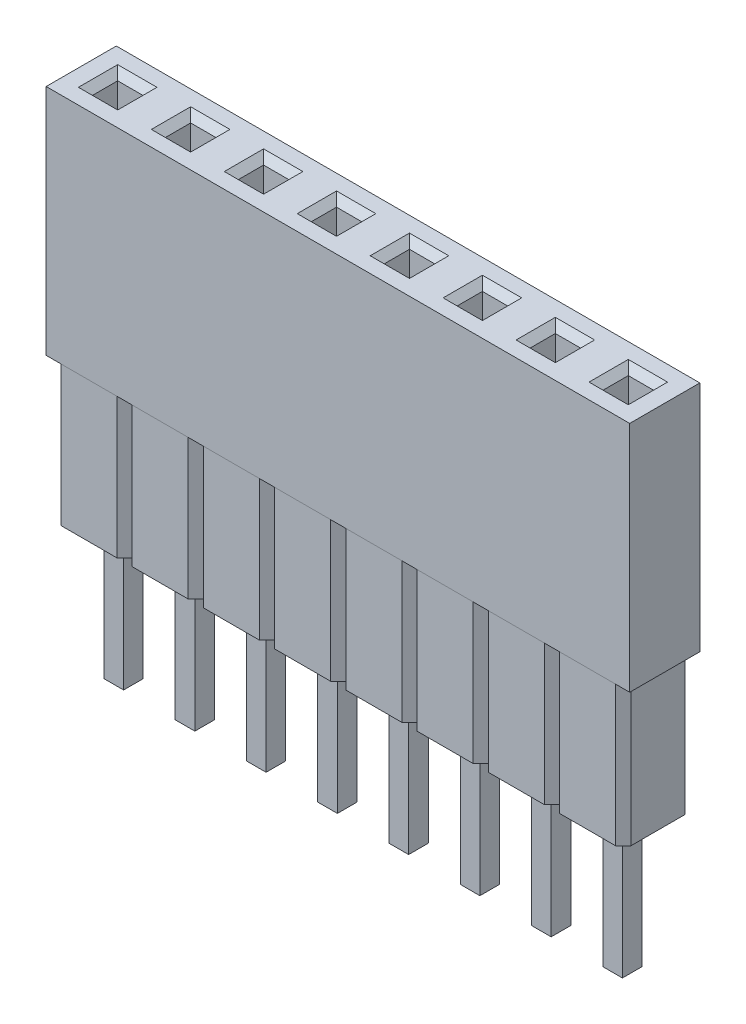
SolidWorks part; units mm, degrees
ref_plane "Alzado" through (0, 0, 0) normal (0, 0, 1) x (1, 0, 0)
ref_plane "Planta" through (0, 0, 0) normal (0, 1, 0) x (1, 0, 0)
ref_plane "Vista lateral" through (0, 0, 0) normal (1, 0, 0) x (0, 0, -1)
sketch "Croquis1" plane through (0, 0, 0) normal (0, 1, 0) x (1, 0, 0)
  line L1 (-10.4, 1.25) -> (10.4, 1.25)
  line L2 (-10.4, 1.25) -> (-10.4, -1.25)
  line L3 (-10.4, -1.25) -> (10.4, -1.25)
  line L4 (10.4, 1.25) -> (10.4, -1.25)
  line L5 (-10.4, 1.25) -> (10.4, -1.25) construction
  line L6 (-10.4, -1.25) -> (10.4, 1.25) construction
  point P0 (0, 0)
  dimension "D1" = 20.8
  dimension "D2" = 2.5
extrude "Saliente-Extruir1" add sketch "Croquis1" along normal blind 8.3
sketch "Croquis3" plane through (0, 8.3, 0) normal (0, 1, 0) x (1, 0, 0)
  line L0 (-10.4, 0) -> (-7.8, 0) construction
  line L1 (-10.4, 1.25) -> (-10.4, -1.25) construction
  line L2 (-7.8, 0) -> (-5.2, 0) construction
  line L3 (-5.2, 0) -> (-2.6, 0) construction
  line L4 (-2.6, 0) -> (0, 0) construction
  line L5 (0, 0) -> (2.6, 0) construction
  line L6 (2.6, 0) -> (5.2, 0) construction
  line L7 (5.2, 0) -> (7.8, 0) construction
  line L8 (7.8, 0) -> (10.4, 0) construction
  line L9 (10.4, -1.25) -> (10.4, 1.25) construction
  line L10 (-9.1, 0) -> (-9.1, 1.25) construction
  line L11 (10.4, 1.25) -> (-10.4, 1.25) construction
  line L12 (-6.5, 0) -> (-6.5, 1.25) construction
  line L13 (-3.9, 0) -> (-3.9, 1.25) construction
  line L14 (-1.3, 0) -> (-1.3, 1.25) construction
  line L15 (1.3, 0) -> (1.3, 1.25) construction
  line L16 (3.9, 0) -> (3.9, 1.25) construction
  line L17 (6.5, 0) -> (6.5, 1.25) construction
  line L18 (9.1, 0) -> (9.1, 1.25) construction
  line L19 (9.1, 1.25) -> (9.0931, 1.2533) construction
  line L21 (-9.8, 0.7) -> (-8.4, 0.7)
  line L22 (-9.8, 0.7) -> (-9.8, -0.7)
  line L23 (-9.8, -0.7) -> (-8.4, -0.7)
  line L24 (-8.4, 0.7) -> (-8.4, -0.7)
  line L25 (-9.8, 0.7) -> (-8.4, -0.7) construction
  line L26 (-9.8, -0.7) -> (-8.4, 0.7) construction
  line L27 (-7.2, 0.7) -> (-5.8, 0.7)
  line L28 (-7.2, 0.7) -> (-7.2, -0.7)
  line L29 (-7.2, -0.7) -> (-5.8, -0.7)
  line L30 (-5.8, 0.7) -> (-5.8, -0.7)
  line L31 (-7.2, 0.7) -> (-5.8, -0.7) construction
  line L32 (-7.2, -0.7) -> (-5.8, 0.7) construction
  line L33 (-4.6, 0.7) -> (-3.2, 0.7)
  line L34 (-4.6, 0.7) -> (-4.6, -0.7)
  line L35 (-4.6, -0.7) -> (-3.2, -0.7)
  line L36 (-3.2, 0.7) -> (-3.2, -0.7)
  line L37 (-4.6, 0.7) -> (-3.2, -0.7) construction
  line L38 (-4.6, -0.7) -> (-3.2, 0.7) construction
  line L39 (-2, 0.7) -> (-0.6, 0.7)
  line L40 (-2, 0.7) -> (-2, -0.7)
  line L41 (-2, -0.7) -> (-0.6, -0.7)
  line L42 (-0.6, 0.7) -> (-0.6, -0.7)
  line L43 (-2, 0.7) -> (-0.6, -0.7) construction
  line L44 (-2, -0.7) -> (-0.6, 0.7) construction
  line L45 (0.6, 0.7) -> (2, 0.7)
  line L46 (0.6, 0.7) -> (0.6, -0.7)
  line L47 (0.6, -0.7) -> (2, -0.7)
  line L48 (2, 0.7) -> (2, -0.7)
  line L49 (0.6, 0.7) -> (2, -0.7) construction
  line L50 (0.6, -0.7) -> (2, 0.7) construction
  line L51 (3.2, 0.7) -> (4.6, 0.7)
  line L52 (3.2, 0.7) -> (3.2, -0.7)
  line L53 (3.2, -0.7) -> (4.6, -0.7)
  line L54 (4.6, 0.7) -> (4.6, -0.7)
  line L55 (3.2, 0.7) -> (4.6, -0.7) construction
  line L56 (3.2, -0.7) -> (4.6, 0.7) construction
  line L57 (5.8, 0.7) -> (7.2, 0.7)
  line L58 (5.8, 0.7) -> (5.8, -0.7)
  line L59 (5.8, -0.7) -> (7.2, -0.7)
  line L60 (7.2, 0.7) -> (7.2, -0.7)
  line L61 (5.8, 0.7) -> (7.2, -0.7) construction
  line L62 (5.8, -0.7) -> (7.2, 0.7) construction
  line L63 (8.4, 0.7) -> (9.8, 0.7)
  line L64 (8.4, 0.7) -> (8.4, -0.7)
  line L65 (8.4, -0.7) -> (9.8, -0.7)
  line L66 (9.8, 0.7) -> (9.8, -0.7)
  line L67 (8.4, 0.7) -> (9.8, -0.7) construction
  line L68 (8.4, -0.7) -> (9.8, 0.7) construction
  dimension "D1" = 2.6
  dimension "D2" = 2.6
  dimension "D3" = 2.6
  dimension "D4" = 2.6
  dimension "D5" = 2.6
  dimension "D6" = 2.6
  dimension "D7" = 2.6
  dimension "D8" = 2.6
  dimension "D9" = 1.4
  dimension "D10" = 1.4
  dimension "D11" = 1.4
  dimension "D12" = 1.4
  dimension "D13" = 1.4
  dimension "D14" = 1.4
  dimension "D15" = 1.4
  dimension "D16" = 1.4
  dimension "D17" = 1.4
  dimension "D18" = 1.4
  dimension "D19" = 1.4
  dimension "D20" = 1.4
  dimension "D21" = 1.4
  dimension "D22" = 1.4
  dimension "D23" = 1.4
  dimension "D24" = 1.4
extrude "Cortar-Extruir1" cut sketch "Croquis3" against normal blind 0.5
sketch "Croquis4" plane through (0, 7.8, 0) normal (0, 1, 0) x (1, 0, 0)
  line L0 (-9.8, 0) -> (9.8, 0) construction
  line L1 (-9.8, 0.7) -> (-9.8, -0.7) construction
  line L2 (9.8, -0.7) -> (9.8, 0.7) construction
  line L3 (9.1, 0.7) -> (9.1, -0.7) construction
  line L4 (9.8, 0.7) -> (8.4, 0.7) construction
  line L5 (8.4, -0.7) -> (9.8, -0.7) construction
  line L6 (6.5, 0.7) -> (6.5, -0.7) construction
  line L7 (7.2, 0.7) -> (5.8, 0.7) construction
  line L8 (5.8, -0.7) -> (7.2, -0.7) construction
  line L9 (3.9, 0.7) -> (3.9, -0.7) construction
  line L12 (1.3, 0.7) -> (1.3, -0.7) construction
  line L13 (2, 0.7) -> (0.6, 0.7) construction
  line L14 (0.6, -0.7) -> (2, -0.7) construction
  line L15 (4.6, 0.7) -> (3.2, 0.7) construction
  line L16 (3.2, -0.7) -> (4.6, -0.7) construction
  line L17 (-1.3, -0.7) -> (-1.3, 0.7) construction
  line L18 (-0.6, 0.7) -> (-2, 0.7) construction
  line L20 (-2, -0.7) -> (-0.6, -0.7) construction
  line L21 (-3.9, 0.7) -> (-3.9, -0.7) construction
  line L22 (-3.2, 0.7) -> (-4.6, 0.7) construction
  line L23 (-4.6, -0.7) -> (-3.2, -0.7) construction
  line L24 (-6.5, 0.7) -> (-6.5, -0.7) construction
  line L25 (-5.8, 0.7) -> (-7.2, 0.7) construction
  line L26 (-7.2, -0.7) -> (-5.8, -0.7) construction
  line L27 (-9.1, 0.7) -> (-9.1, -0.7) construction
  line L28 (-8.4, 0.7) -> (-9.8, 0.7) construction
  line L29 (-9.8, -0.7) -> (-8.4, -0.7) construction
  line L30 (-9.1, 0) -> (-6.5, 0) construction
  line L31 (-9.55, 0.45) -> (-8.65, 0.45)
  line L32 (-9.55, 0.45) -> (-9.55, -0.45)
  line L33 (-9.55, -0.45) -> (-8.65, -0.45)
  line L34 (-8.65, 0.45) -> (-8.65, -0.45)
  line L35 (-9.55, 0.45) -> (-8.65, -0.45) construction
  line L36 (-9.55, -0.45) -> (-8.65, 0.45) construction
  line L37 (-6.95, 0.45) -> (-6.05, 0.45)
  line L38 (-6.95, 0.45) -> (-6.95, -0.45)
  line L39 (-6.95, -0.45) -> (-6.05, -0.45)
  line L40 (-6.05, 0.45) -> (-6.05, -0.45)
  line L41 (-6.95, 0.45) -> (-6.05, -0.45) construction
  line L42 (-6.95, -0.45) -> (-6.05, 0.45) construction
  line L43 (-3.45, -0.45) -> (-4.35, -0.45)
  line L44 (-3.45, -0.45) -> (-3.45, 0.45)
  line L45 (-3.45, 0.45) -> (-4.35, 0.45)
  line L46 (-4.35, -0.45) -> (-4.35, 0.45)
  line L47 (-3.45, -0.45) -> (-4.35, 0.45) construction
  line L48 (-3.45, 0.45) -> (-4.35, -0.45) construction
  line L49 (-0.85, -0.45) -> (-1.75, -0.45)
  line L50 (-0.85, -0.45) -> (-0.85, 0.45)
  line L51 (-0.85, 0.45) -> (-1.75, 0.45)
  line L52 (-1.75, -0.45) -> (-1.75, 0.45)
  line L53 (-0.85, -0.45) -> (-1.75, 0.45) construction
  line L54 (-0.85, 0.45) -> (-1.75, -0.45) construction
  line L55 (1.75, -0.45) -> (0.85, -0.45)
  line L56 (1.75, -0.45) -> (1.75, 0.45)
  line L57 (1.75, 0.45) -> (0.85, 0.45)
  line L58 (0.85, -0.45) -> (0.85, 0.45)
  line L59 (1.75, -0.45) -> (0.85, 0.45) construction
  line L60 (1.75, 0.45) -> (0.85, -0.45) construction
  line L61 (4.35, -0.45) -> (3.45, -0.45)
  line L62 (4.35, -0.45) -> (4.35, 0.45)
  line L63 (4.35, 0.45) -> (3.45, 0.45)
  line L64 (3.45, -0.45) -> (3.45, 0.45)
  line L65 (4.35, -0.45) -> (3.45, 0.45) construction
  line L66 (4.35, 0.45) -> (3.45, -0.45) construction
  line L67 (6.05, 0.45) -> (6.95, 0.45)
  line L68 (6.05, 0.45) -> (6.05, -0.45)
  line L69 (6.05, -0.45) -> (6.95, -0.45)
  line L70 (6.95, 0.45) -> (6.95, -0.45)
  line L71 (6.05, 0.45) -> (6.95, -0.45) construction
  line L72 (6.05, -0.45) -> (6.95, 0.45) construction
  line L73 (8.65, 0.45) -> (9.55, 0.45)
  line L74 (8.65, 0.45) -> (8.65, -0.45)
  line L75 (8.65, -0.45) -> (9.55, -0.45)
  line L76 (9.55, 0.45) -> (9.55, -0.45)
  line L77 (8.65, 0.45) -> (9.55, -0.45) construction
  line L78 (8.65, -0.45) -> (9.55, 0.45) construction
  point P54 (-9.1, 0)
  point P59 (-6.5, 0)
  point P64 (-3.9, 0)
  point P69 (-1.3, 0)
  point P74 (1.3, 0)
  point P79 (3.9, 0)
  point P84 (6.5, 0)
  point P89 (9.1, 0)
  dimension "D1" = 0.9
  dimension "D2" = 0.9
  dimension "D3" = 0.9
  dimension "D4" = 0.9
  dimension "D5" = 0.9
  dimension "D6" = 0.9
  dimension "D7" = 0.9
  dimension "D8" = 0.9
  dimension "D9" = 0.9
  dimension "D10" = 0.9
  dimension "D11" = 0.9
  dimension "D12" = 0.9
  dimension "D13" = 0.9
  dimension "D14" = 0.9
  dimension "D15" = 0.9
  dimension "D16" = 0.9
extrude "Cortar-Extruir2" cut sketch "Croquis4" against normal blind 6.5
chamfer "Chaflán2" distance 0.5 angle 45 4 edges at (-9.1, 7.8, 0.7) (-8.4, 7.8, 0) (-9.8, 7.8, 0) (-9.1, 7.8, -0.7)
chamfer "Chaflán3" distance 0.5 angle 45 4 edges at (-6.5, 7.8, 0.7) (-7.2, 7.8, 0) (-5.8, 7.8, 0) (-6.5, 7.8, -0.7)
chamfer "Chaflán4" distance 0.5 angle 45 4 edges at (-3.9, 7.8, 0.7) (-3.2, 7.8, 0) (-3.9, 7.8, -0.7) (-4.6, 7.8, 0)
chamfer "Chaflán5" distance 0.5 angle 45 4 edges at (-0.6, 7.8, 0) (-1.3, 7.8, -0.7) (-2, 7.8, 0) (-1.3, 7.8, 0.7)
chamfer "Chaflán6" distance 0.5 angle 45 4 edges at (1.3, 7.8, 0.7) (0.6, 7.8, 0) (1.3, 7.8, -0.7) (2, 7.8, 0)
chamfer "Chaflán7" distance 0.5 angle 45 4 edges at (4.6, 7.8, 0) (3.9, 7.8, -0.7) (3.9, 7.8, 0.7) (3.2, 7.8, 0)
chamfer "Chaflán8" distance 0.5 angle 45 4 edges at (6.5, 7.8, 0.7) (7.2, 7.8, 0) (6.5, 7.8, -0.7) (5.8, 7.8, 0)
chamfer "Chaflán9" distance 0.5 angle 45 4 edges at (9.8, 7.8, 0) (9.1, 7.8, -0.7) (8.4, 7.8, 0) (9.1, 7.8, 0.7)
sketch "Croquis5" plane through (0, 0, 0) normal (0, -1, 0) x (1, 0, 0)
  line L0 (-10.4, 0) -> (0, 0) construction
  line L1 (-10.4, -1.25) -> (-10.4, 1.25) construction
  line L2 (0, 0) -> (0, 1.25) construction
  line L3 (-10.4, 1.25) -> (10.4, 1.25) construction
  line L5 (-10.16, 1.24) -> (10.16, 1.24)
  line L6 (-10.16, 1.24) -> (-10.16, -1.24)
  line L7 (-10.16, -1.24) -> (10.16, -1.24)
  line L8 (10.16, 1.24) -> (10.16, -1.24)
  line L9 (-10.16, 1.24) -> (10.16, -1.24) construction
  line L10 (-10.16, -1.24) -> (10.16, 1.24) construction
  dimension "D1" = 20.32
  dimension "D2" = 2.48
extrude "Saliente-Extruir2" add sketch "Croquis5" along normal blind 5
sketch "Croquis6" plane through (0, -5, 0) normal (0, -1, 0) x (1, 0, 0)
  line L0 (-10.16, 1.24) -> (-7.62, 1.24) construction
  line L1 (10.16, 1.24) -> (-10.16, 1.24) construction
  line L2 (-7.62, 1.24) -> (-5.08, 1.24) construction
  line L3 (10.16, 1.24) -> (-10.16, 1.24) construction
  line L4 (-5.08, 1.24) -> (-2.54, 1.24) construction
  line L5 (-2.54, 1.24) -> (0, 1.24) construction
  line L6 (0, 1.24) -> (2.54, 1.24) construction
  line L7 (2.54, 1.24) -> (5.08, 1.24) construction
  line L8 (5.08, 1.24) -> (7.62, 1.24) construction
  line L9 (-10.16, 0) -> (10.16, 0) construction
  line L10 (-10.16, 1.24) -> (-10.16, -1.24) construction
  line L11 (10.16, -1.24) -> (10.16, 1.24) construction
  line L12 (-10.16, 1.24) -> (-10.16, 0.97)
  line L13 (-10.16, 0.97) -> (-9.89, 1.24)
  line L14 (-9.89, 1.24) -> (-10.16, 1.24)
  line L15 (-10.16, -1.24) -> (-10.16, -0.97)
  line L16 (-10.16, -0.97) -> (-9.89, -1.24)
  line L17 (-10.16, -1.24) -> (10.16, -1.24) construction
  line L18 (-9.89, -1.24) -> (-10.16, -1.24)
  line L19 (-10.16, 0.97) -> (10.16, 0.97) construction
  line L20 (-10.16, -0.97) -> (10.16, -0.97) construction
  line L21 (-7.62, 1.24) -> (-7.89, 1.24)
  line L22 (-7.89, 1.24) -> (-7.62, 0.97)
  line L23 (-7.62, 0.97) -> (-7.35, 1.24)
  line L24 (-7.35, 1.24) -> (-7.62, 1.24)
  line L25 (-5.08, 1.24) -> (-5.35, 1.24)
  line L26 (-5.35, 1.24) -> (-5.08, 0.97)
  line L27 (-5.08, 0.97) -> (-4.81, 1.24)
  line L28 (-4.81, 1.24) -> (-5.08, 1.24)
  line L29 (-2.54, 1.24) -> (-2.81, 1.24)
  line L30 (-2.81, 1.24) -> (-2.54, 0.97)
  line L31 (-2.54, 0.97) -> (-2.27, 1.24)
  line L32 (-2.27, 1.24) -> (-2.54, 1.24)
  line L33 (0, 1.24) -> (-0.27, 1.24)
  line L34 (-0.27, 1.24) -> (0, 0.97)
  line L35 (0, 0.97) -> (0.27, 1.24)
  line L36 (0.27, 1.24) -> (0, 1.24)
  line L37 (2.54, 1.24) -> (2.27, 1.24)
  line L38 (2.27, 1.24) -> (2.54, 0.97)
  line L39 (2.54, 0.97) -> (2.81, 1.24)
  line L40 (2.81, 1.24) -> (2.54, 1.24)
  line L41 (5.08, 1.24) -> (4.81, 1.24)
  line L42 (4.81, 1.24) -> (5.08, 0.97)
  line L43 (5.08, 0.97) -> (5.35, 1.24)
  line L44 (5.35, 1.24) -> (5.08, 1.24)
  line L45 (7.62, 1.24) -> (7.35, 1.24)
  line L46 (7.35, 1.24) -> (7.62, 0.97)
  line L47 (7.62, 0.97) -> (7.89, 1.24)
  line L48 (7.89, 1.24) -> (7.62, 1.24)
  line L49 (10.16, 1.24) -> (9.89, 1.24)
  line L50 (9.89, 1.24) -> (10.16, 0.97)
  line L51 (10.16, 0.97) -> (10.16, 1.24)
  line L52 (10.16, -1.24) -> (9.89, -1.24)
  line L53 (9.89, -1.24) -> (10.16, -0.97)
  line L54 (10.16, -0.97) -> (10.16, -1.24)
  line L56 (7.62, -0.97) -> (7.35, -1.24)
  line L57 (7.35, -1.24) -> (7.62, -1.25)
  line L58 (10.4, -1.25) -> (-10.4, -1.25) construction
  line L59 (7.62, -1.25) -> (7.89, -1.24)
  line L60 (7.89, -1.24) -> (7.62, -0.97)
  line L61 (5.08, -0.97) -> (5.35, -1.24)
  line L62 (-10.16, -1.24) -> (10.16, -1.24) construction
  line L63 (5.35, -1.24) -> (4.81, -1.24)
  line L64 (4.81, -1.24) -> (5.08, -0.97)
  line L65 (2.54, -0.97) -> (2.27, -1.24)
  line L66 (2.27, -1.24) -> (2.81, -1.24)
  line L67 (2.81, -1.24) -> (2.54, -0.97)
  line L68 (0, -0.97) -> (0.27, -1.24)
  line L69 (0.27, -1.24) -> (-0.27, -1.24)
  line L70 (-0.27, -1.24) -> (0, -0.97)
  line L71 (-2.54, -0.97) -> (-2.27, -1.24)
  line L72 (-2.27, -1.24) -> (-2.81, -1.24)
  line L73 (-2.81, -1.24) -> (-2.54, -0.97)
  line L74 (-5.08, -0.97) -> (-5.35, -1.24)
  line L75 (-5.35, -1.24) -> (-4.81, -1.24)
  line L76 (-4.81, -1.24) -> (-5.08, -0.97)
  line L77 (-7.62, -0.97) -> (-7.89, -1.24)
  line L78 (-7.89, -1.24) -> (-7.35, -1.24)
  line L79 (-7.35, -1.24) -> (-7.62, -0.97)
  dimension "D1" = 2.54
  dimension "D2" = 2.54
  dimension "D3" = 2.54
  dimension "D4" = 2.54
  dimension "D5" = 2.54
  dimension "D6" = 2.54
  dimension "D7" = 2.54
  dimension "D8" = 0.27
  dimension "D9" = 0.27
  dimension "D10" = 0.27
  dimension "D11" = 0.27
  dimension "D12" = 0.27
  dimension "D13" = 0.27
  dimension "D14" = 0.27
  dimension "D15" = 0.27
  dimension "D16" = 0.27
  dimension "D17" = 0.27
  dimension "D18" = 0.27
  dimension "D19" = 0.27
  dimension "D20" = 0.27
  dimension "D21" = 0.27
  dimension "D22" = 0.27
  dimension "D23" = 0.27
  dimension "D24" = 0.27
  dimension "D25" = 0.27
  dimension "D26" = 0.27
  dimension "D27" = 0.27
  dimension "D28" = 0.27
  dimension "D29" = 0.54
  dimension "D30" = 0.54
extrude "Cortar-Extruir3" cut sketch "Croquis6" against normal blind 5
sketch "Croquis7" plane through (0, -5, 0) normal (0, -1, 0) x (1, 0, 0)
  line L0 (-10.16, 0) -> (10.16, 0) construction
  line L1 (-10.16, 0.97) -> (-10.16, -0.97) construction
  line L2 (10.16, -0.97) -> (10.16, 0.97) construction
  line L3 (-8.89, 1.24) -> (-8.89, -1.24) construction
  line L4 (-7.89, 1.24) -> (-9.89, 1.24) construction
  line L5 (-9.89, -1.24) -> (-7.89, -1.24) construction
  line L6 (-6.35, 1.24) -> (-6.35, -1.24) construction
  line L7 (-5.35, 1.24) -> (-7.35, 1.24) construction
  line L8 (-7.35, -1.24) -> (-5.35, -1.24) construction
  line L9 (-3.81, 1.24) -> (-3.81, -1.24) construction
  line L10 (-2.81, 1.24) -> (-4.81, 1.24) construction
  line L11 (-4.81, -1.24) -> (-2.81, -1.24) construction
  line L12 (-1.27, 1.24) -> (-1.27, -1.24) construction
  line L13 (-0.27, 1.24) -> (-2.27, 1.24) construction
  line L14 (-2.27, -1.24) -> (-0.27, -1.24) construction
  line L15 (1.27, 1.24) -> (1.27, -1.24) construction
  line L16 (2.27, 1.24) -> (0.27, 1.24) construction
  line L17 (0.27, -1.24) -> (2.27, -1.24) construction
  line L18 (3.81, 1.24) -> (3.81, -1.24) construction
  line L19 (4.81, 1.24) -> (2.81, 1.24) construction
  line L20 (2.81, -1.24) -> (4.81, -1.24) construction
  line L21 (6.35, 1.24) -> (6.35, -1.24) construction
  line L22 (7.35, 1.24) -> (5.35, 1.24) construction
  line L23 (5.35, -1.24) -> (7.35, -1.24) construction
  line L24 (8.89, 1.24) -> (8.89, -1.24) construction
  line L25 (9.89, 1.24) -> (7.89, 1.24) construction
  line L26 (7.89, -1.24) -> (9.89, -1.24) construction
  line L28 (-9.24, 0.35) -> (-8.54, 0.35)
  line L29 (-9.24, 0.35) -> (-9.24, -0.35)
  line L30 (-9.24, -0.35) -> (-8.54, -0.35)
  line L31 (-8.54, 0.35) -> (-8.54, -0.35)
  line L32 (-9.24, 0.35) -> (-8.54, -0.35) construction
  line L33 (-9.24, -0.35) -> (-8.54, 0.35) construction
  line L34 (-6.7, 0.35) -> (-6, 0.35)
  line L35 (-6.7, 0.35) -> (-6.7, -0.35)
  line L36 (-6.7, -0.35) -> (-6, -0.35)
  line L37 (-6, 0.35) -> (-6, -0.35)
  line L38 (-6.7, 0.35) -> (-6, -0.35) construction
  line L39 (-6.7, -0.35) -> (-6, 0.35) construction
  line L40 (-3.46, -0.35) -> (-4.16, -0.35)
  line L41 (-3.46, -0.35) -> (-3.46, 0.35)
  line L42 (-3.46, 0.35) -> (-4.16, 0.35)
  line L43 (-4.16, -0.35) -> (-4.16, 0.35)
  line L44 (-3.46, -0.35) -> (-4.16, 0.35) construction
  line L45 (-3.46, 0.35) -> (-4.16, -0.35) construction
  line L46 (-1.62, 0.35) -> (-0.92, 0.35)
  line L47 (-1.62, 0.35) -> (-1.62, -0.35)
  line L48 (-1.62, -0.35) -> (-0.92, -0.35)
  line L49 (-0.92, 0.35) -> (-0.92, -0.35)
  line L50 (-1.62, 0.35) -> (-0.92, -0.35) construction
  line L51 (-1.62, -0.35) -> (-0.92, 0.35) construction
  line L52 (0.92, 0.35) -> (1.62, 0.35)
  line L53 (0.92, 0.35) -> (0.92, -0.35)
  line L54 (0.92, -0.35) -> (1.62, -0.35)
  line L55 (1.62, 0.35) -> (1.62, -0.35)
  line L56 (0.92, 0.35) -> (1.62, -0.35) construction
  line L57 (0.92, -0.35) -> (1.62, 0.35) construction
  line L58 (4.16, -0.35) -> (3.46, -0.35)
  line L59 (4.16, -0.35) -> (4.16, 0.35)
  line L60 (4.16, 0.35) -> (3.46, 0.35)
  line L61 (3.46, -0.35) -> (3.46, 0.35)
  line L62 (4.16, -0.35) -> (3.46, 0.35) construction
  line L63 (4.16, 0.35) -> (3.46, -0.35) construction
  line L64 (6.7, -0.35) -> (6, -0.35)
  line L65 (6.7, -0.35) -> (6.7, 0.35)
  line L66 (6.7, 0.35) -> (6, 0.35)
  line L67 (6, -0.35) -> (6, 0.35)
  line L68 (6.7, -0.35) -> (6, 0.35) construction
  line L69 (6.7, 0.35) -> (6, -0.35) construction
  line L70 (9.24, -0.35) -> (8.54, -0.35)
  line L71 (9.24, -0.35) -> (9.24, 0.35)
  line L72 (9.24, 0.35) -> (8.54, 0.35)
  line L73 (8.54, -0.35) -> (8.54, 0.35)
  line L74 (9.24, -0.35) -> (8.54, 0.35) construction
  line L75 (9.24, 0.35) -> (8.54, -0.35) construction
  point P54 (-8.89, 0)
  point P59 (-6.35, 0)
  point P64 (-3.81, 0)
  point P69 (-1.27, 0)
  point P74 (1.27, 0)
  point P79 (3.81, 0)
  point P84 (6.35, 0)
  point P89 (8.89, 0)
  dimension "D1" = 0.7
  dimension "D2" = 0.7
  dimension "D3" = 0.7
  dimension "D4" = 0.7
  dimension "D5" = 0.7
  dimension "D6" = 0.7
  dimension "D7" = 0.7
  dimension "D8" = 0.7
  dimension "D9" = 0.7
  dimension "D10" = 0.7
  dimension "D11" = 0.7
  dimension "D12" = 0.7
  dimension "D13" = 0.7
  dimension "D14" = 0.7
  dimension "D15" = 0.7
  dimension "D16" = 0.7
extrude "Saliente-Extruir3" add sketch "Croquis7" along normal blind 4.85
